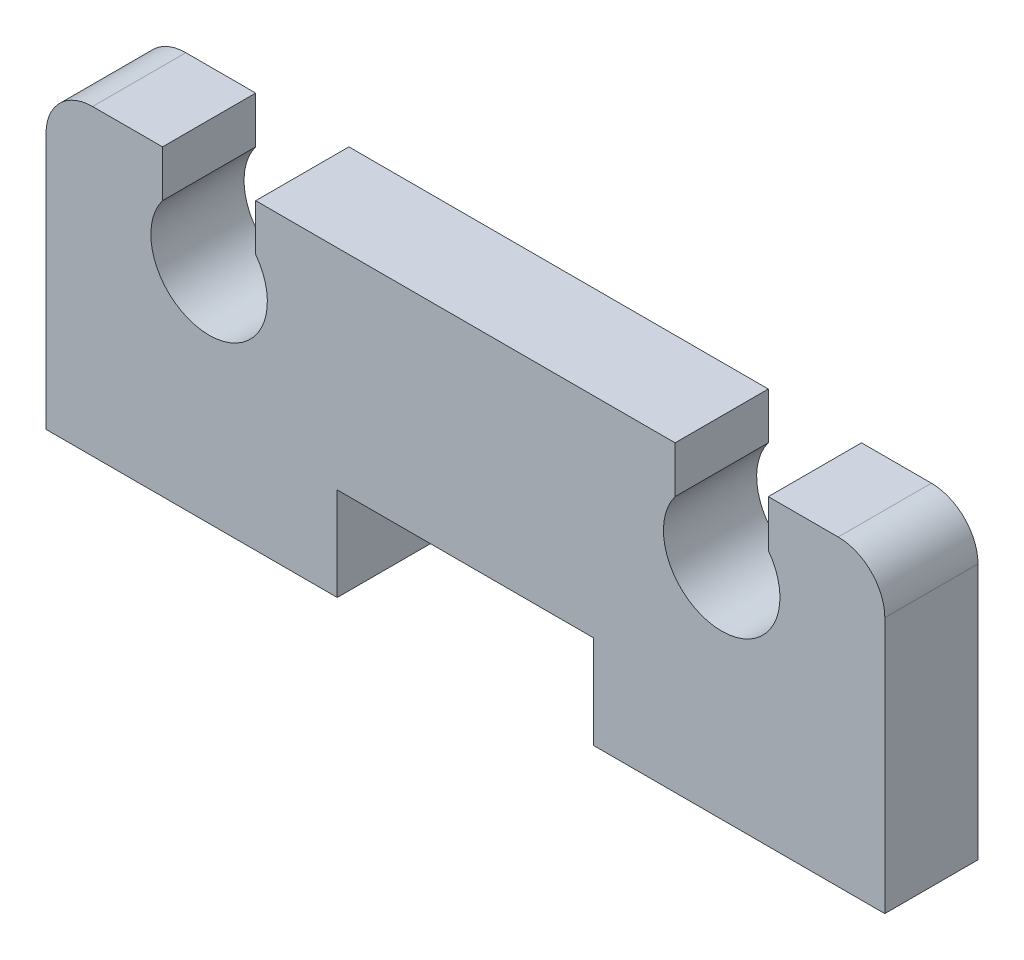
SolidWorks part; units mm, degrees
ref_plane "Front Plane" through (0, 0, 0) normal (0, 0, 1) x (1, 0, 0)
ref_plane "Top Plane" through (0, 0, 0) normal (0, 1, 0) x (1, 0, 0)
ref_plane "Right Plane" through (0, 0, 0) normal (1, 0, 0) x (0, 0, -1)
sketch "Sketch1" plane through (0, 0, 0) normal (0, 0, 1) x (1, 0, 0)
  line L14 (-9, 0) -> (-9, 6.5)
  line L15 (-9, 6.5) -> (-6.5, 6.5)
  line L16 (-9, 0) -> (-2.75, 0)
  line L17 (-2.75, 0) -> (-2.75, 2)
  line L18 (-2.75, 2) -> (2.75, 2)
  line L19 (0, 6.5) -> (0, 0) construction
  line L20 (-6.5, 5.5) -> (-6.5, 6.5)
  line L21 (-4.5, 5.5) -> (-4.5, 6.5)
  line L22 (-4.5, 6.5) -> (4.5, 6.5)
  line L23 (4.5, 5.5) -> (4.5, 6.5)
  line L24 (6.5, 5.5) -> (6.5, 6.5)
  line L25 (2.75, 0) -> (2.75, 2)
  line L26 (9, 0) -> (2.75, 0)
  line L27 (9, 6.5) -> (6.5, 6.5)
  line L28 (9, 0) -> (9, 6.5)
  arc A4 (-6.5, 5.5) -> (-4.5, 5.5) centre (-5.5, 4.75) ccw
  arc A5 (6.5, 5.5) -> (4.5, 5.5) centre (5.5, 4.75) cw
  point P41 (0, 2)
  dimension "D2" = 9
  dimension "D10" = 1.25
  dimension "D3" = 2
  dimension "D4" = 1.75
  dimension "D5" = 2
  dimension "D6" = 6.5
  dimension "D7" = 6.25
  dimension "D9" = 3.5
extrude "Tube Plate Body" add sketch "Sketch1" along normal blind 2
fillet "Tube Plate Contouring" radius 1 2 edges at (9, 6.5, 1) (-9, 6.5, 1)
equation "\"D2@Sketch1\"=\"Wph@Parameters@RobotHandParameters.SLDPRT\"/2"
equation "\"D6@Sketch1\"=\"rp@Parameters@RobotHandParameters.SLDPRT\" - 2 - \"Tjointp@Parameters@RobotHandParameters.SLDPRT\"/2 + 1.75"
